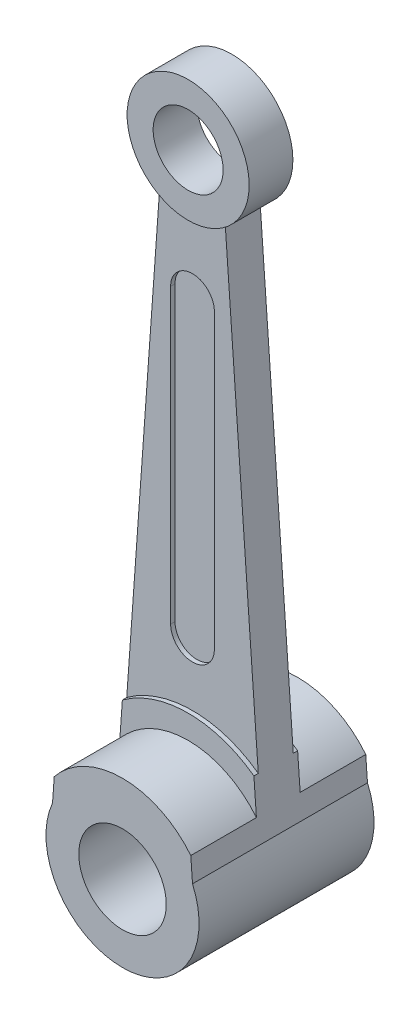
SolidWorks part; units mm, degrees
ref_plane "Front Plane" through (0, 0, 0) normal (0, 0, 1) x (1, 0, 0)
ref_plane "Top Plane" through (0, 0, 0) normal (0, 1, 0) x (1, 0, 0)
ref_plane "Right Plane" through (0, 0, 0) normal (1, 0, 0) x (0, 0, -1)
sketch "Sketch1" plane through (0, 0, 0) normal (0, 0, 1) x (1, 0, 0)
  line L0 (1.8632, 104.3243) -> (1.8632, -32.5757) construction
  line L1 (-5.6368, 92.5619) -> (-14.6368, -13.2649)
  line L2 (9.3632, 92.5619) -> (18.3632, -13.2649)
  line L3 (1.8632, 74.3243) -> (1.8632, 7.4243) construction
  line L4 (6.8632, 74.3243) -> (6.8632, 7.4243)
  line L5 (-3.1368, 74.3243) -> (-3.1368, 7.4243)
  circle A0 centre (1.8632, -32.5757) radius 25.4
  circle A1 centre (1.8632, -32.5757) radius 10
  circle A2 centre (1.8632, 104.3243) radius 8
  circle A3 centre (1.8632, 104.3243) radius 13.95
  arc A4 (6.8632, 74.3243) -> (-3.1368, 74.3243) centre (1.8632, 74.3243) ccw
  arc A5 (-3.1368, 7.4243) -> (6.8632, 7.4243) centre (1.8632, 7.4243) ccw
  point P12 (1.8632, 40.8743)
  dimension "D1" = 50.8
  dimension "D2" = 20
  dimension "D3" = 16
  dimension "D4" = 27.9
  dimension "D7" = 5
  dimension "D5" = 136.9
  dimension "D6" = 15
  dimension "D8" = 30
  dimension "D9" = 40
  dimension "D10" = 33
extrude "Boss-Extrude1" add sketch "Sketch1" against normal mid plane 10 contours A0 A1 | A3 A2 region at (-4.6544, 116.21, 0) region at (1.8632, -7.8942, 0)
extrude "Boss-Extrude2" add sketch "Sketch1<3>" along normal mid plane 8 contours A3 L1 A0 L2 A5 L5 A4 L4 region at (1.8632, 89.2657, 0)
sketch "Sketch1<3>" plane through (0, 0, 0) normal (0, 0, 1) x (1, 0, 0) same geometry as "Sketch1"
extrude "Boss-Extrude3" add sketch "Sketch1<4>" along normal mid plane 6 contours L5 A5 L4 A4 region at (1.8632, 40.8743, 0)
sketch "Sketch1<4>" plane through (0, 0, 0) normal (0, 0, 1) x (1, 0, 0) same geometry as "Sketch1"
sketch "Sketch3" plane through (0, 0, 5) normal (0, 0, 1) x (1, 0, 0)
  circle A0 centre (1.8632, -32.5757) radius 10
  circle A1 centre (1.8632, -32.5757) radius 20
  dimension "D1" = 40
  dimension "D2" = 20
extrude "Boss-Extrude4" add sketch "Sketch3" along normal blind 15 and the other way blind 25
sketch "Sketch4" plane through (0, 0, 0) normal (0, 0, 1) x (1, 0, 0)
  line L0 (-5.6368, 92.5619) -> (-25.0969, -6.5105)
  line L1 (9.3632, 92.5619) -> (28.8234, -6.5105)
  line L2 (-5.6368, 92.5619) -> (-14.1368, -25.487)
  line L3 (9.3632, 92.5619) -> (17.8632, -25.487)
  arc A0 (-14.1368, -25.487) -> (17.8632, -25.487) centre (1.8632, -32.5757) ccw
  arc A1 (-25.0969, -6.5105) -> (28.8234, -6.5105) centre (1.8632, -32.5757) ccw
  circle A2 centre (1.8632, 104.3243) radius 13.95 construction
  arc A3 (-5.6368, 92.5619) -> (9.3632, 92.5619) centre (1.8632, 104.3243) ccw construction
  dimension "D1" = 17.5
  dimension "D3" = 37.5
  dimension "D2" = 32
extrude "Cut-Extrude1" cut sketch "Sketch4" against normal mid plane 55
scale "Scale2" bodies to scale 107 scale about centroid uniform scaling yes scale factor 0.1
